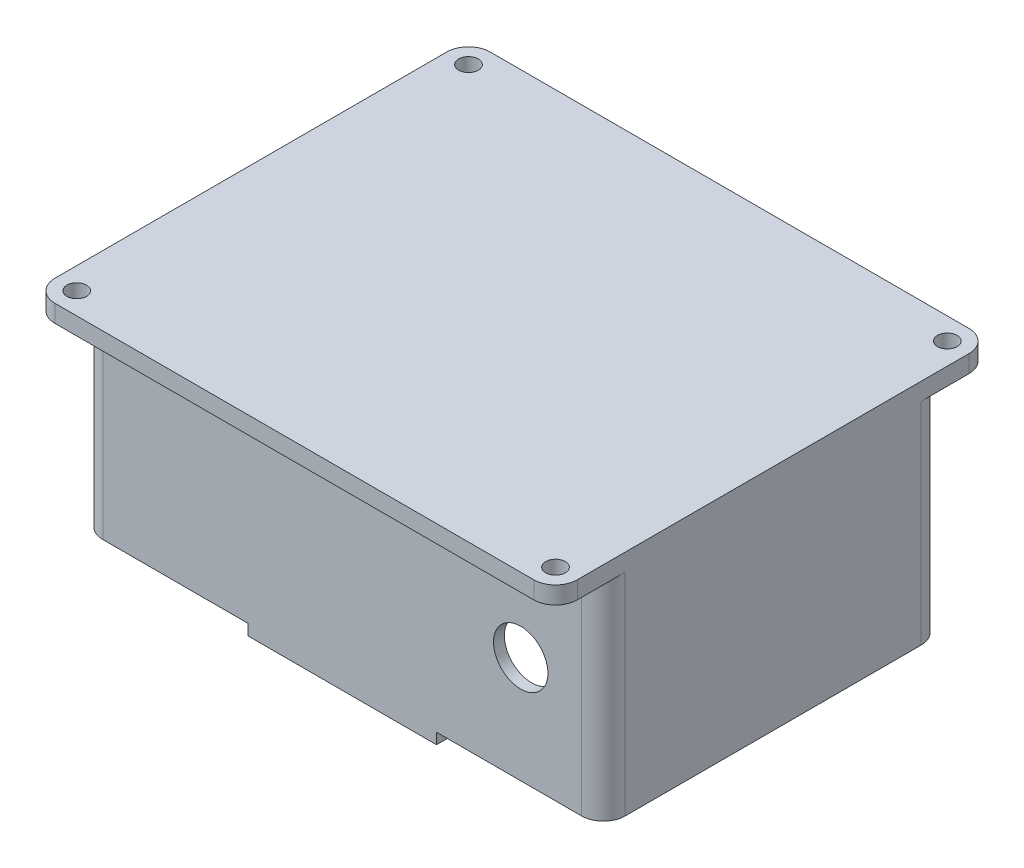
SolidWorks part; units mm, degrees
ref_plane "Přední" through (0, 0, 0) normal (0, 0, 1) x (1, 0, 0)
ref_plane "Horní" through (0, 0, 0) normal (0, 1, 0) x (1, 0, 0)
ref_plane "Pravá" through (0, 0, 0) normal (1, 0, 0) x (0, 0, -1)
sketch "Skica1" plane through (0, 1.6, 0) normal (0, 1, 0) x (1, 0, 0)
  line L0 (1.524, 65.776) -> (1.524, 8.636) construction
  line L1 (-4.318, 76.206) -> (115.682, 76.206)
  line L2 (-4.318, 76.206) -> (-4.318, -1.794)
  line L3 (-4.318, -1.794) -> (115.682, -1.794)
  line L4 (115.682, 76.206) -> (115.682, -1.794)
  line L6 (-4.318, 37.206) -> (1.524, 37.206) construction
  line L7 (1.524, 65.776) -> (1.524, 8.636) construction
  dimension "D1" = 78
  dimension "D2" = 120
  dimension "D3" = 5.842
extrude "Přidat vysunutím1" add sketch "Skica1" against normal blind 55 from offset 14
sketch "Skica2" plane through (0, 15.6, 0) normal (0, 1, 0) x (1, 0, 0)
  line L0 (-4.318, 76.206) -> (-4.318, -1.794) construction
  line L1 (-4.318, 87.206) -> (115.682, 87.206)
  line L2 (-4.318, 87.206) -> (-4.318, -12.794)
  line L3 (-4.318, -12.794) -> (115.682, -12.794)
  line L4 (115.682, 87.206) -> (115.682, -12.794)
  line L5 (115.682, -1.794) -> (115.682, 76.206) construction
  line L6 (115.682, 37.206) -> (-4.318, 37.206) construction
  dimension "D1" = 100
extrude "Přidat vysunutím2" add sketch "Skica2" against normal blind 4
fillet "Zaoblit1" radius 5 8 edges at (115.682, -13.9, -76.206) (-4.318, 13.6, -87.206) (-4.318, -13.9, -76.206) (-4.318, -13.9, 1.794) (-4.318, 13.6, 12.794) (115.682, 13.6, 12.794) (115.682, 13.6, -87.206) (115.682, -13.9, 1.794)
shell "Skořepina1" thickness 2.5 removed face at (55.682, -39.4, -37.206)
sketch "Skica3" plane through (113.888, 0, 1.794) normal (0, 0, -1) x (-1, 0, 0)
  line L0 (-1.794, 11.6) -> (-1.794, -39.4) construction
  line L2 (113.206, -39.4) -> (3.206, -39.4) construction
  circle A0 centre (17.206, -12.4) radius 6.25
  dimension "D1" = 12.5
  dimension "D2" = 19
  dimension "D3" = 27
extrude "Odebrat vysunutím1" cut sketch "Skica3" along normal blind 3
sketch "Skica4" plane through (0, -39.4, 0) normal (0, -1, 0) x (1, 0, 0)
  line L16 (77.332, -65.806) -> (77.332, -76.206)
  line L17 (77.332, -76.206) -> (110.682, -76.206)
  line L18 (115.682, -71.206) -> (115.682, -3.206)
  line L19 (110.682, 1.794) -> (77.332, 1.794)
  line L20 (77.332, 1.794) -> (77.332, -8.606)
  line L21 (77.332, -8.606) -> (34.032, -8.606)
  line L22 (34.032, -8.606) -> (34.032, 1.794)
  line L23 (34.032, 1.794) -> (0.682, 1.794)
  line L24 (-4.318, -3.206) -> (-4.318, -15.556)
  line L25 (-4.318, -15.556) -> (6.082, -15.556)
  line L26 (6.082, -15.556) -> (6.082, -58.856)
  line L27 (6.082, -58.856) -> (-4.318, -58.856)
  line L28 (-4.318, -58.856) -> (-4.318, -71.206)
  line L29 (0.682, -76.206) -> (34.032, -76.206)
  line L30 (34.032, -76.206) -> (34.032, -65.806)
  line L31 (34.032, -65.806) -> (77.332, -65.806)
  line L32 (77.332, -65.806) -> (77.332, -76.206)
  line L33 (77.332, -76.206) -> (110.682, -76.206)
  line L34 (115.682, -71.206) -> (115.682, -3.206)
  line L35 (110.682, 1.794) -> (77.332, 1.794)
  line L36 (77.332, 1.794) -> (77.332, -8.606)
  line L37 (77.332, -8.606) -> (34.032, -8.606)
  line L38 (34.032, -8.606) -> (34.032, 1.794)
  line L39 (34.032, 1.794) -> (0.682, 1.794)
  line L40 (-4.318, -3.206) -> (-4.318, -15.556)
  line L41 (-4.318, -15.556) -> (6.082, -15.556)
  line L42 (6.082, -15.556) -> (6.082, -58.856)
  line L43 (6.082, -58.856) -> (-4.318, -58.856)
  line L44 (-4.318, -58.856) -> (-4.318, -71.206)
  line L45 (0.682, -76.206) -> (34.032, -76.206)
  line L46 (34.032, -76.206) -> (34.032, -65.806)
  line L47 (34.032, -65.806) -> (77.332, -65.806)
  arc A4 (110.682, -76.206) -> (115.682, -71.206) centre (110.682, -71.206) ccw
  arc A5 (115.682, -3.206) -> (110.682, 1.794) centre (110.682, -3.206) ccw
  arc A6 (0.682, 1.794) -> (-4.318, -3.206) centre (0.682, -3.206) ccw
  arc A7 (-4.318, -71.206) -> (0.682, -76.206) centre (0.682, -71.206) ccw
  arc A8 (110.682, -76.206) -> (115.682, -71.206) centre (110.682, -71.206) ccw
  arc A9 (115.682, -3.206) -> (110.682, 1.794) centre (110.682, -3.206) ccw
  arc A10 (0.682, 1.794) -> (-4.318, -3.206) centre (0.682, -3.206) ccw
  arc A11 (-4.318, -71.206) -> (0.682, -76.206) centre (0.682, -71.206) ccw
  dimension "D1" = 0
extrude "Odebrat vysunutím2" cut sketch "Skica4" against normal blind 2.5
sketch "Skica5" plane through (0, -36.9, 0) normal (0, -1, 0) x (1, 0, 0)
  line L0 (0.682, -73.706) -> (4.182, -73.706)
  line L1 (34.032, -73.706) -> (0.682, -73.706) construction
  line L2 (4.182, -73.706) -> (4.182, -67.706)
  line L3 (4.182, -67.706) -> (-1.818, -67.706)
  line L4 (-1.818, -71.206) -> (-1.818, -58.856) construction
  line L5 (-1.818, -67.706) -> (-1.818, -71.206)
  line L6 (-1.818, -3.206) -> (-1.818, -6.706)
  line L7 (-1.818, -71.206) -> (-1.818, -3.206) construction
  line L8 (-1.818, -6.706) -> (4.182, -6.706)
  line L9 (4.182, -6.706) -> (4.182, -0.706)
  line L10 (0.682, -0.706) -> (34.032, -0.706) construction
  line L11 (4.182, -0.706) -> (0.682, -0.706)
  line L12 (110.682, -73.706) -> (107.182, -73.706)
  line L13 (110.682, -73.706) -> (77.332, -73.706) construction
  line L14 (107.182, -73.706) -> (107.182, -67.706)
  line L15 (107.182, -67.706) -> (113.182, -67.706)
  line L16 (113.182, -3.206) -> (113.182, -71.206) construction
  line L17 (113.182, -67.706) -> (113.182, -71.206)
  line L18 (113.182, -3.206) -> (113.182, -6.706)
  line L19 (113.182, -3.206) -> (113.182, -71.206) construction
  line L20 (113.182, -6.706) -> (107.182, -6.706)
  line L21 (107.182, -6.706) -> (107.182, -0.706)
  line L22 (0.682, -0.706) -> (110.682, -0.706) construction
  line L23 (107.182, -0.706) -> (110.682, -0.706)
  arc A0 (110.682, -73.706) -> (113.182, -71.206) centre (110.682, -71.206) ccw construction
  arc A1 (113.182, -3.206) -> (110.682, -0.706) centre (110.682, -3.206) ccw construction
  arc A2 (-1.818, -71.206) -> (0.682, -73.706) centre (0.682, -71.206) ccw construction
  arc A3 (0.682, -0.706) -> (-1.818, -3.206) centre (0.682, -3.206) ccw construction
  arc A4 (110.682, -73.706) -> (113.182, -71.206) centre (110.682, -71.206) ccw
  arc A5 (113.182, -3.206) -> (110.682, -0.706) centre (110.682, -3.206) ccw
  arc A6 (-1.818, -71.206) -> (0.682, -73.706) centre (0.682, -71.206) ccw
  arc A7 (0.682, -0.706) -> (-1.818, -3.206) centre (0.682, -3.206) ccw
  dimension "D1" = 6
extrude "Přidat vysunutím3" add sketch "Skica5" against normal blind 15
chamfer "Zkosení1" distance 6 angle 45 4 edges at (107.182, -21.9, -70.706) (107.182, -21.9, -3.706) (4.182, -21.9, -3.706) (4.182, -21.9, -70.706)
fillet "Zaoblit2" radius 3 4 edges at (4.182, -32.4, -6.706) (107.182, -32.4, -6.706) (4.182, -32.4, -67.706) (107.182, -32.4, -67.706)
hole_wizard "Ø2.4 (2.4) průměr díry2" positions "Skica7" profile "Skica6" hole size "Ø2.4" standard "DIN"
sketch "Skica7" plane through (0, -36.9, 0) normal (0, -1, 0) x (-1, 0, 0)
  point P0 (-0.682, 3.206)
  point P3 (-110.682, 3.206)
  point P6 (-110.682, 71.206)
  point P9 (-0.682, 71.206)
sketch "Skica6" plane through (0.682, -36.9, -3.206) normal (1, 0, 0) x (0, 0, -1)
  line L0 (0, 0) -> (0, 20)
  line L1 (0, 20) -> (1.2, 20)
  line L2 (1.2, 20) -> (1.2, 0)
  line L5 (1.2, 0) -> (0, 0)
  line L10 (0, 20) -> (-1.2, 20) construction
  line L11 (0, -6.35) -> (0, 107.95) construction
  dimension "Průměr díry" = 2.4
  dimension "Hloubka díry" = 20
  dimension "Úhel vrtání" = 180
fillet "Zaoblit3" radius 1 8 edges at (4.182, -32.4, -0.706) (-1.818, -29.4, -6.706) (-1.818, -29.4, -67.706) (4.182, -32.4, -73.706) (113.182, -29.4, -67.706) (107.182, -32.4, -73.706) (107.182, -32.4, -0.706) (113.182, -29.4, -6.706)
sketch "Skica8" plane through (0, 13.1, 0) normal (0, -1, 0) x (1, 0, 0)
  circle A0 centre (4.064, -11.176) radius 4
  circle A1 centre (4.064, -61.976) radius 4
  circle A2 centre (86.868, -61.976) radius 4
  circle A3 centre (86.868, -11.176) radius 4
  dimension "D1" = 8
extrude "Přidat vysunutím4" add sketch "Skica8" along normal up to surface (11.5 mm away)
fillet "Zaoblit4" radius 2 12 edges at (55.682, 13.1, -73.706) (-1.0858, 13.1, -72.9738) (-1.818, 13.1, -37.206) (-1.0858, 13.1, -1.4382) (55.682, 13.1, -0.706) (112.4498, 13.1, -1.4382) (113.182, 13.1, -37.206) (112.4498, 13.1, -72.9738) (4.064, 13.1, -7.176) (4.064, 13.1, -57.976) (86.868, 13.1, -57.976) (86.868, 13.1, -7.176)
chamfer "Zkosení2" distance 1 angle 79 4 edges at (4.064, 1.6, -57.976) (86.868, 1.6, -57.976) (86.868, 1.6, -7.176) (4.064, 1.6, -7.176) first distance on face at (4.064, 1.6, -57.976) first distance on face at (86.868, 1.6, -57.976) first distance on face at (86.868, 1.6, -7.176) first distance on face at (4.064, 1.6, -7.176)
hole_wizard "Ø2.4 (2.4) průměr díry1" positions "Skica10" profile "Skica9" hole size "Ø2.4" standard "DIN"
sketch "Skica10" plane through (0, 1.6, 0) normal (0, -1, 0) x (-1, 0, 0)
  point P0 (-86.868, 61.976)
  point P3 (-4.064, 61.976)
  point P6 (-4.064, 11.176)
  point P9 (-86.868, 11.176)
sketch "Skica9" plane through (86.868, 1.6, -61.976) normal (1, 0, 0) x (0, 0, -1)
  line L0 (0, 0) -> (0, 10)
  line L1 (0, 10) -> (1.2, 10)
  line L2 (1.2, 10) -> (1.2, 0)
  line L5 (1.2, 0) -> (0, 0)
  line L10 (0, 10) -> (-1.2, 10) construction
  line L11 (0, -6.35) -> (0, 107.95) construction
  dimension "Průměr díry" = 2.4
  dimension "Hloubka díry" = 10
  dimension "Úhel vrtání" = 180
hole_wizard "Ø4.5 (4.5) průměr díry1" positions "Skica12" profile "Skica11" hole size "Ø4.5" standard "DIN"
sketch "Skica12" plane through (0, 11.6, 0) normal (0, -1, 0) x (-1, 0, 0)
  point P0 (-110.682, 82.206)
  point P3 (-0.682, 82.206)
  point P6 (-0.682, -7.794)
  point P9 (-110.682, -7.794)
sketch "Skica11" plane through (110.682, 11.6, -82.206) normal (1, 0, 0) x (0, 0, -1)
  line L0 (0, 0) -> (0, 20)
  line L1 (0, 20) -> (2.25, 20)
  line L2 (2.25, 20) -> (2.25, 0)
  line L5 (2.25, 0) -> (0, 0)
  line L10 (0, 20) -> (-2.25, 20) construction
  line L11 (0, -6.35) -> (0, 107.95) construction
  dimension "Průměr díry" = 4.5
  dimension "Hloubka díry" = 20
  dimension "Úhel vrtání" = 180
